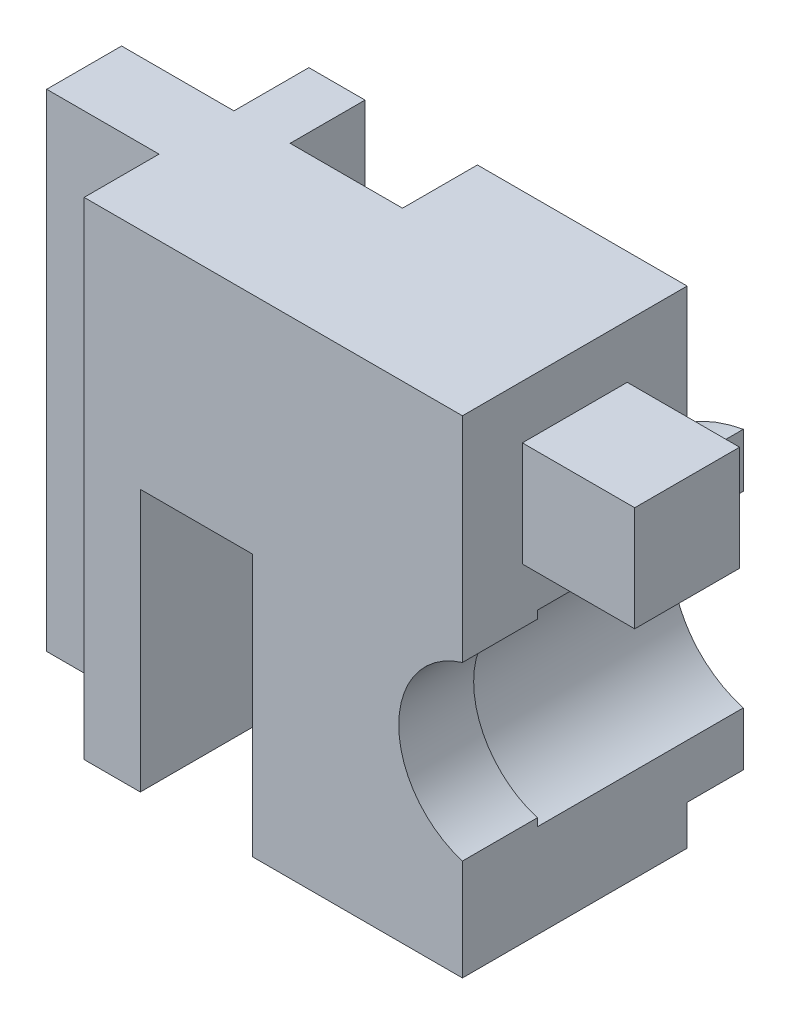
SolidWorks part; units mm, degrees
note: The reader was unsure of these and kept them because the rebuilt part matched: shared geometry of "Sketch17<2>".
ref_plane "Front Plane" through (0, 0, 0) normal (0, 0, 1) x (1, 0, 0)
ref_plane "Top Plane" through (0, 0, 0) normal (0, 1, 0) x (1, 0, 0)
ref_plane "Right Plane" through (0, 0, 0) normal (1, 0, 0) x (0, 0, -1)
sketch "Sketch1" plane through (0, 0, 0) normal (0, 0, 1) x (1, 0, 0)
  line L0 (-11.5, 0) -> (11.5, 0) construction
  line L1 (3.75, -5) -> (14.7, -5)
  line L2 (-14.7, -5) -> (-3.75, -5)
  line L3 (-14.7, -5) -> (-14.7, 8)
  line L4 (-14.7, 8) -> (14.7, 8)
  line L5 (14.7, -5) -> (14.7, 8)
  line L6 (-17.6832, -10.5909) -> (24.7009, -10.5909)
  line L7 (-24.9768, -7) -> (25.0232, -7) construction
  line L8 (-24.9768, -7) -> (-24.9768, -5) construction
  line L9 (-24.9768, -5) -> (-3.75, -5) construction
  line L10 (25.0232, -7) -> (25.0232, -5) construction
  line L11 (-24.9768, -7) -> (25.0232, -5) construction
  line L12 (-24.9768, -5) -> (25.0232, -7) construction
  line L13 (-5.1, -3.6128) -> (-5.1, 3.6128)
  line L14 (9, -3) -> (14, -3) construction
  line L15 (9, -3) -> (9, 3) construction
  line L16 (9, 3) -> (14, 3) construction
  line L17 (14, -3) -> (14, 3) construction
  line L18 (9, -3) -> (14, 3) construction
  line L19 (9, 3) -> (14, -3) construction
  line L20 (5.1, -3.6128) -> (5.1, 3.6128)
  line L21 (-5.1, -3.6128) -> (5.1, 3.6128) construction
  line L22 (-5.1, 3.6128) -> (5.1, -3.6128) construction
  line L23 (3.75, -5) -> (25.0232, -5) construction
  circle A0 centre (0, 0) radius 2 construction
  circle A1 centre (11.5, 0) radius 9.5 construction
  circle A2 centre (-11.5, 0) radius 9.5 construction
  circle A3 centre (11.5, 0) radius 10.5909 construction
  circle A4 centre (-11.5, 0) radius 10.5909 construction
  circle A5 centre (0, 0) radius 0.5
  circle A6 centre (-11.5, 0) radius 1
  circle A7 centre (11.5, 0) radius 1
  arc A8 (5.1, 3.6128) -> (-5.1, 3.6128) centre (0, 0) ccw
  arc A9 (-5.1, -3.6128) -> (-3.75, -5) centre (0, 0) ccw
  arc A10 (3.75, -5) -> (5.1, -3.6128) centre (0, 0) ccw
  point P13 (0, 0)
  point P17 (0, 8)
  point P18 (0.0232, -6)
  point P29 (3.5089, -10.5909)
  dimension "D1" = 4
  dimension "D2" = 19
  dimension "D5" = 1
  dimension "D6" = 2
  dimension "D9" = 12.5
  dimension "D3" = 13
  dimension "D4" = 2
  dimension "D7" = 5
  dimension "D8" = 6
  dimension "D10" = 10.2
  dimension "D11" = 8
  dimension "D12" = 3.2
extrude "Boss-Extrude1" add sketch "Sketch1" along normal blind 6 contours A10 L1 L5 L4 L3 L2 A9 L13 A8 L20 A7 A6
sketch "Sketch2" plane through (0, 0, 0) normal (0, 0, 1) x (1, 0, 0)
  circle A0 centre (-11.5, 0) radius 2.6
  circle A1 centre (11.5, 0) radius 2.6
  dimension "D1" = 5.2
extrude "Cut-Extrude1" cut sketch "Sketch2" along normal blind 6
sketch "Sketch3" plane through (0, 0, 0) normal (0, 0, 1) x (1, 0, 0)
  line L0 (-14.7, -5) -> (-3.75, -5) construction
  line L1 (-14.7, 8) -> (-22.3, 8)
  line L2 (-14.7, 8) -> (-14.7, -5)
  line L3 (-14.7, -5) -> (-22.3, -5)
  line L4 (-22.3, 8) -> (-22.3, -5)
  dimension "D1" = 7.6
extrude "Boss-Extrude2" add sketch "Sketch3" along normal blind 6
sketch "Sketch6" plane through (0, 0, 0) normal (0, 1, 0) x (1, 0, 0)
  line L0 (-22.3, -6) -> (-22.3, 0) construction
  line L1 (-22.3, -2) -> (-25.3, -2)
  line L2 (-22.3, -2) -> (-22.3, -4)
  line L3 (-22.3, -4) -> (-25.3, -4)
  line L4 (-25.3, -2) -> (-25.3, -4)
  line L5 (14.7, -6) -> (14.7, 0) construction
  line L6 (14.7, -2) -> (17.7, -2)
  line L7 (14.7, -2) -> (14.7, -4)
  line L8 (14.7, -4) -> (17.7, -4)
  line L9 (17.7, -2) -> (17.7, -4)
  point P12 (-22.3, -3)
  point P13 (-22.3, -3)
  dimension "D1" = 2
  dimension "D2" = 3
extrude "Boss-Extrude5" add sketch "Sketch6" along normal up to surface (13 mm away) from surface
sketch "Sketch10" plane through (0, 0, 6) normal (0, 0, 1) x (1, 0, 0)
  line L0 (14.7, 2.4) -> (14.7, -2.4)
  line L2 (14.7, -5) -> (14.7, 8) construction
  circle A0 centre (-11.5, 0) radius 2.6
  circle A1 centre (11.5, 0) radius 2.6
  circle A2 centre (-11.5, 0) radius 2.6 construction
  circle A3 centre (11.5, 0) radius 2.6 construction
  arc A4 (14.7, 2.4) -> (14.7, -2.4) centre (11.5, 0) ccw
  circle A5 centre (-11.5, 0) radius 4
  dimension "D1" = 8
extrude "Boss-Extrude6" add sketch "Sketch10" against normal blind 1.5 from surface at -6 starting at face at (-8.9, 0, 0)
sketch "Sketch12" plane through (0, 0, 0) normal (0, 0, -1) x (-1, 0, 0)
  circle A0 centre (-11.5, 0) radius 2.4
  circle A1 centre (11.5, 0) radius 2.4
  circle A2 centre (11.5, 0) radius 2.6
  circle A3 centre (-11.5, 0) radius 2.6
  circle A4 centre (-11.5, 0) radius 2.6 construction
  circle A5 centre (11.5, 0) radius 2.6 construction
  dimension "D1" = 4.8
extrude "Boss-Extrude7" add sketch "Sketch12" along normal blind 2 from surface at -6 starting at face at (-8.9, 0, 6)
sketch "Sketch13" plane through (0, -5, 0) normal (0, -1, 0) x (1, 0, 0)
  line L12 (-22.3, 6) -> (-3.75, 6) construction
  line L13 (-22.3, 0) -> (-16.3, 0)
  line L14 (-22.3, 0) -> (-22.3, 2)
  line L15 (-22.3, 2) -> (-20.8, 2)
  line L16 (-16.3, 0) -> (-16.3, 2)
  line L18 (-20.8, 2) -> (-20.8, 6)
  line L19 (-20.8, 6) -> (-17.8, 6)
  line L20 (-17.8, 2) -> (-17.8, 6)
  line L21 (-17.8, 2) -> (-16.3, 2)
  dimension "D1" = 6
  dimension "D2" = 3
  dimension "D3" = 2
extrude "Cut-Extrude2" cut sketch "Sketch13" against normal blind 7
sketch "Sketch14" plane through (0, 0, 0) normal (0, 0, -1) x (-1, 0, 0)
  line L0 (22.3, 8) -> (-14.7, 8) construction
  line L1 (20.8, 2) -> (17.8, 2)
  line L2 (20.8, 2) -> (20.8, 8)
  line L3 (20.8, 8) -> (17.8, 8)
  line L4 (17.8, 2) -> (17.8, 8)
  line L5 (17.8, 2) -> (17.8, -5) construction
extrude "Cut-Extrude3" cut sketch "Sketch14" against normal blind 2
sketch "Sketch15" plane through (0, 0, 0) normal (0, 0, 1) x (1, 0, 0)
  line L0 (-17.8, 8) -> (14.7, 8) construction
  line L1 (-12, -5) -> (-12.2, -5)
  line L2 (-12, -5) -> (-12, 8)
  line L3 (-12, 8) -> (-12.2, 8)
  line L4 (-12.2, -5) -> (-12.2, 8)
  line L5 (-12, -5) -> (-12.2, 8) construction
  line L6 (-12, 8) -> (-12.2, -5) construction
  line L7 (3.75, -5) -> (14.7, -5) construction
  line L8 (12, -5) -> (12.2, -5)
  line L9 (12, -5) -> (12, 8)
  line L10 (12, 8) -> (12.2, 8)
  line L11 (12.2, -5) -> (12.2, 8)
  line L12 (12, -5) -> (12.2, 8) construction
  line L13 (12, 8) -> (12.2, -5) construction
  circle A0 centre (-11.5, 0) radius 2.4 construction
  circle A1 centre (11.5, 0) radius 2.4 construction
  point P0 (-12.1, 1.5)
  point P7 (12.1, 1.5)
  dimension "D1" = 0.2
  dimension "D2" = 0.5
  dimension "D3" = 0.5
extrude "Cut-Extrude5" cut sketch "Sketch15" against normal mid plane 15
sketch "Sketch16" plane through (12, 0, 0) normal (1, 0, 0) x (0, 0, -1)
  line L0 (0, 8) -> (-6, 2.3473) construction
  line L2 (-1.5, 3.6737) -> (-4.5, 3.6737)
  line L3 (-1.5, 3.6737) -> (-1.5, 6.6737)
  line L4 (-1.5, 6.6737) -> (-4.5, 6.6737)
  line L5 (-4.5, 3.6737) -> (-4.5, 6.6737)
  line L6 (-1.5, 3.6737) -> (-4.5, 6.6737) construction
  line L7 (-1.5, 6.6737) -> (-4.5, 3.6737) construction
  point P4 (-3, 5.1737)
  dimension "D1" = 3
extrude "Cut-Extrude6" cut sketch "Sketch16" against normal blind 3
mirror "Mirror1" about plane through (0, 0, 0) normal (1, 0, 0) of "Cut-Extrude6"
sketch "Sketch17" plane through (-12.2, 0, 0) normal (1, 0, 0) x (0, 0, -1)
  line L0 (-4.5, 6.6737) -> (-1.5, 3.6737) construction
  line L2 (-4.4, 3.7737) -> (-1.6, 3.7737)
  line L3 (-4.4, 3.7737) -> (-4.4, 6.5737)
  line L4 (-4.4, 6.5737) -> (-1.6, 6.5737)
  line L5 (-1.6, 3.7737) -> (-1.6, 6.5737)
  line L6 (-4.4, 3.7737) -> (-1.6, 6.5737) construction
  line L7 (-4.4, 6.5737) -> (-1.6, 3.7737) construction
  point P4 (-3, 5.1737)
  dimension "D1" = 2.8
extrude "Boss-Extrude9" add sketch "Sketch17" along normal blind 3
extrude "Boss-Extrude10" add sketch "Sketch17<2>" against normal blind 3 from surface at 24.4 starting at face at (12.2, -3.4345, 2.125)
sketch "Sketch17<2>" plane through (-12.2, 0, 0) normal (1, 0, 0) x (0, 0, -1) same geometry as "Sketch17"
sketch "Sketch18" plane through (0, 0, 0) normal (0, 0, 1) x (1, 0, 0)
  line L5 (17.7, 8) -> (-12, 8)
  line L6 (17.7, 8) -> (17.7, -5)
  line L7 (17.7, -5) -> (-12, -5)
  line L8 (-12, 8) -> (-12, -5)
  point P0 (0, 0)
extrude "Cut-Extrude11" cut sketch "Sketch18" against normal mid plane 18
sketch "Sketch21" plane through (-12.2, 0, 0) normal (1, 0, 0) x (0, 0, -1)
  line L1 (-4.4, 6.5737) -> (-1.6, 6.5737)
  line L2 (-4.4, 6.5737) -> (-4.4, 3.7737)
  line L3 (-4.4, 3.7737) -> (-1.6, 3.7737)
  line L4 (-1.6, 6.5737) -> (-1.6, 3.7737)
extrude "Boss-Extrude12" add sketch "Sketch21" along normal blind 3
